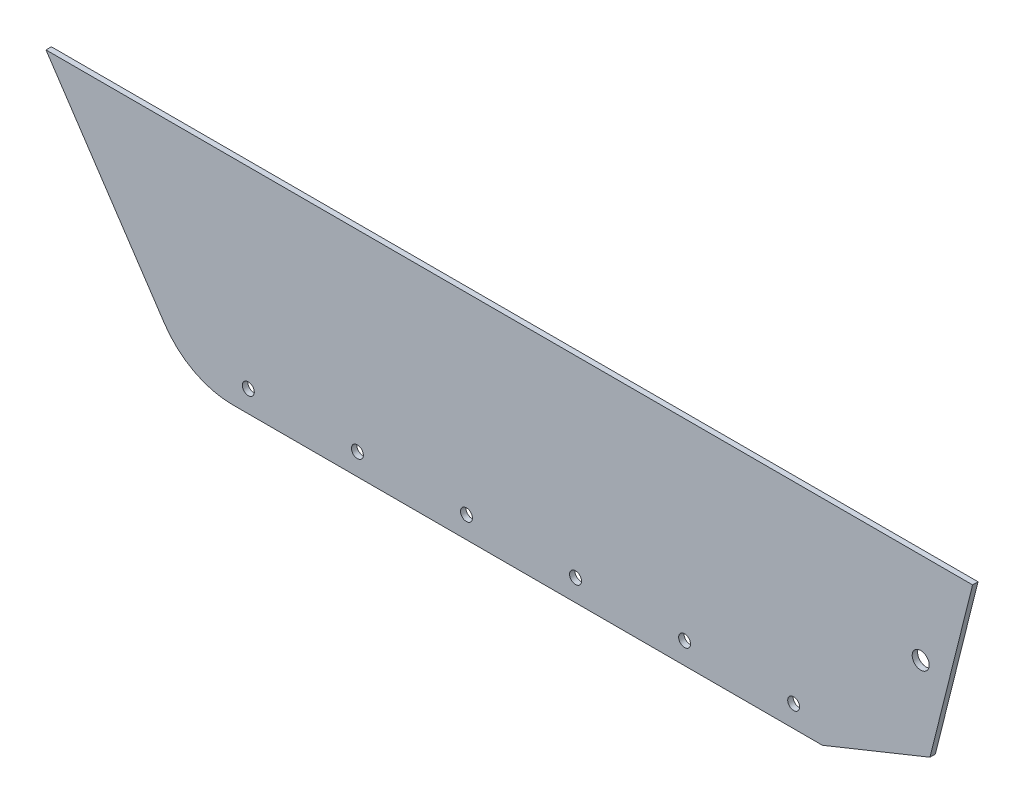
SolidWorks part; units mm, degrees
material "5052-H34"
ref_plane "Front Plane" through (0, 0, 0) normal (0, 0, 1) x (1, 0, 0)
ref_plane "Top Plane" through (0, 0, 0) normal (0, 1, 0) x (1, 0, 0)
ref_plane "Right Plane" through (0, 0, 0) normal (1, 0, 0) x (0, 0, -1)
sketch "Sketch1" plane through (0, 0, 0) normal (0, 0, 1) x (1, 0, 0)
  line L6 (-98.8794, 3.851) -> (-31.8794, -96.649)
  line L7 (428.1206, 28.9396) -> (403.1206, -71.149)
  line L9 (403.1206, -71.149) -> (366, -96.649)
  line L10 (-31.8794, -96.649) -> (366, -96.649)
  line L12 (-98.8794, 3.851) -> (-115.6052, 28.9396)
  line L13 (-115.6052, 28.9396) -> (428.1206, 28.9396)
  circle A0 centre (3.1206, -83.899) radius 3.5
  circle A1 centre (67.1206, -83.899) radius 3.5
  circle A2 centre (131.1206, -83.899) radius 3.5
  circle A3 centre (195.1206, -83.899) radius 3.5
  circle A4 centre (259.1206, -83.899) radius 3.5
  circle A5 centre (323.1206, -83.899) radius 3.5
  point P0 (-48.8794, -71.149)
  point P2 (-31.8794, -96.649)
  point P8 (48, -83.899)
  point P9 (403.1206, -71.149)
  dimension "D2" = 64
  dimension "D4" = 64
  dimension "D14" = 7
  dimension "D1" = 25.5
  dimension "D3" = 75
  dimension "D5" = 25
  dimension "D6" = 80
  dimension "D7" = 527
  dimension "D8" = 180
  dimension "D9" = 64
  dimension "D10" = 64
  dimension "D11" = 64
  dimension "D12" = 123.69
  dimension "D13" = 12.75
  dimension "D15" = 366
  dimension "D16" = 115.6052
extrude "Boss-Extrude1" add sketch "Sketch1" along normal blind 3.175 contours L12 L13 L7 L9 L10 L6
extrude "Cut-Extrude1" cut sketch "Sketch1<4>" along normal through all contours A0 | A1 | A2 | A3 | A4 | A5 region at (3.1206, -83.899, 0)
sketch "Sketch1<4>" plane through (0, 0, 0) normal (0, 0, 1) x (1, 0, 0) same geometry as "Sketch1"
sketch "Sketch2" plane through (0, 0, 0) normal (0, 0, -1) x (-1, 0, 0)
  circle A0 centre (-291.1206, -83.899) radius 6.5
  circle A2 centre (-241.5603, -124.3932) radius 6.5
  circle A3 centre (-192, -83.899) radius 6.5
  circle A4 centre (-128, -83.899) radius 6.5
  circle A5 centre (-64, -83.899) radius 6.5
  circle A6 centre (0, -83.899) radius 6.5
  dimension "D2" = 0
  dimension "D3" = 64
  dimension "D4" = 64
  dimension "D5" = 64
  dimension "D6" = 64
  dimension "D7" = 64
  dimension "D8" = 13
  dimension "D1" = 32
sketch "Sketch5" plane through (0, 0, 0) normal (0, 0, -1) x (-1, 0, 0)
  line L0 (48.8794, -71.149) -> (-14.2353, -96.649)
  line L1 (31.8794, -96.649) -> (-366, -96.649) construction
  line L2 (-14.2353, -96.649) -> (31.8794, -96.649)
  line L3 (31.8794, -96.649) -> (48.8794, -71.149)
  line L6 (-366, -96.649) -> (-403.1206, -71.149)
  line L7 (-403.1206, -71.149) -> (-352, -71.149)
  line L9 (-352, -71.149) -> (-326.5, -96.649)
  line L11 (-366, -96.649) -> (-326.5, -96.649)
  dimension "D1" = 22
  dimension "D2" = 45
extrude "Cut-Extrude2" [suppressed] cut sketch "Sketch5" against normal up to next
sketch "Sketch6" plane through (0, 0, 3.175) normal (0, 0, 1) x (1, 0, 0)
  line L0 (-48.8794, -71.149) -> (14.2353, -96.649)
  line L1 (-31.8794, -96.649) -> (366, -96.649) construction
  line L2 (14.2353, -96.649) -> (-31.8794, -96.649)
  line L3 (-31.8794, -96.649) -> (-48.8794, -71.149)
  dimension "D1" = 158
fillet "Fillet1" radius 48 1 edges at (-31.8794, -96.649, 1.5875)
sketch "Sketch7" plane through (0, 0, 3.175) normal (0, 0, 1) x (1, 0, 0)
  line L0 (403.1206, -71.149) -> (340.0059, -96.649)
  line L1 (-31.8794, -96.649) -> (366, -96.649) construction
  line L2 (340.0059, -96.649) -> (366, -96.649)
  line L3 (366, -96.649) -> (403.1206, -71.149)
  dimension "D1" = 22
extrude "Cut-Extrude3" cut sketch "Sketch7" against normal blind 10
sketch "Sketch9" plane through (0, 0, 0) normal (0, 0, -1) x (-1, 0, 0)
  line L0 (-403.1206, -71.149) -> (48.8794, -71.149)
  line L1 (48.8794, -71.149) -> (48.8794, -114.9143)
  line L2 (48.8794, -114.9143) -> (-403.1206, -114.9143)
  line L3 (-403.1206, -114.9143) -> (-403.1206, -71.149)
sketch "Sketch11" plane through (0, 0, 0) normal (0, 0, -1) x (-1, 0, 0)
  circle A0 centre (-397.6786, -24.6104) radius 5
extrude "Cut-Extrude5" cut sketch "Sketch11" against normal up to next
sketch "Sketch12" plane through (0, 0, 3.175) normal (0, 0, 1) x (1, 0, 0)
  line L1 (875.2623, -24.6104) -> (-79.9052, -24.6104)
  line L2 (-115.6052, 28.9396) -> (-46.129, -75.2746) construction
  line L3 (-6.1906, -96.649) -> (340.0059, -96.649) construction
  circle A0 centre (397.6786, -24.6104) radius 5 construction
  circle A1 centre (397.6786, -24.6104) radius 5
  point P8 (397.6786, -24.6104)
  point P10 (-64.9052, -24.6104)
  dimension "D1" = 15
